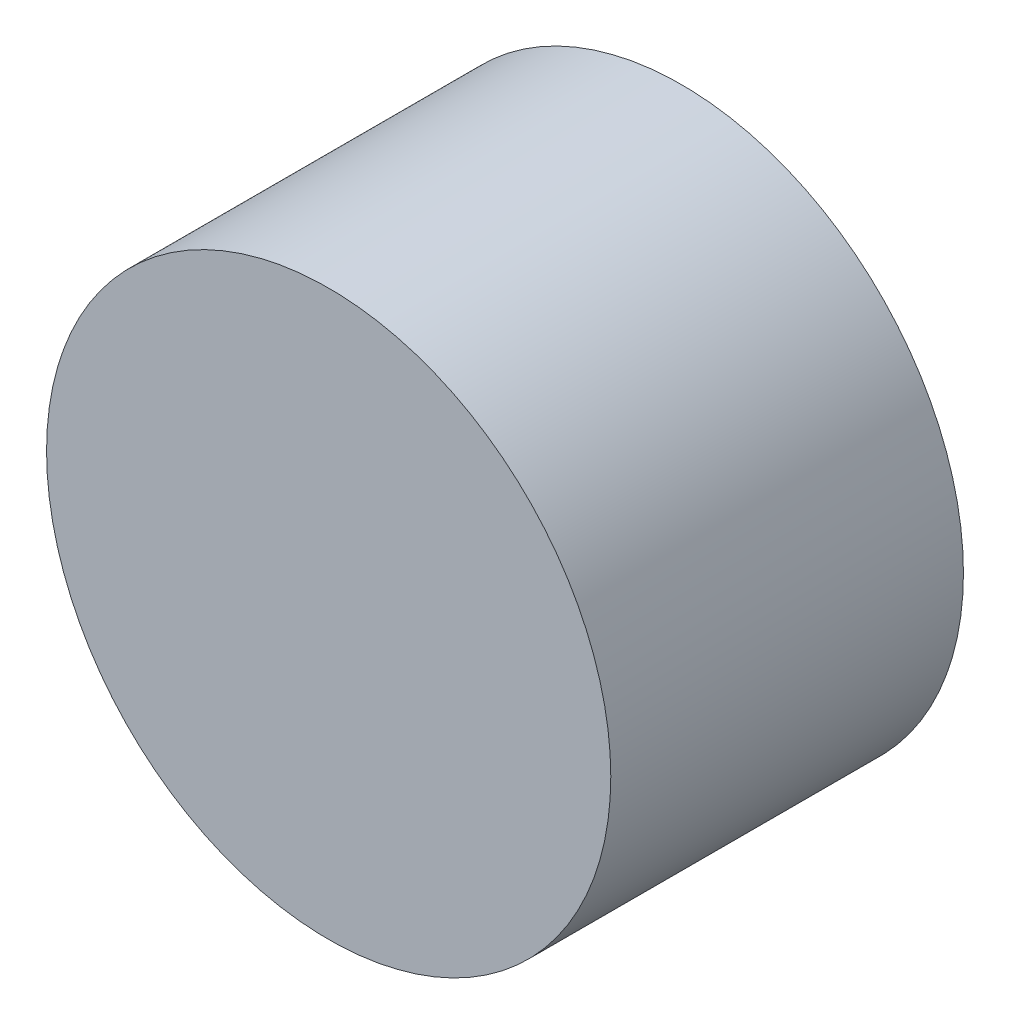
SolidWorks part; units mm, degrees
material "Pure Lead"
ref_plane "XY" through (0, 0, 0) normal (0, 0, 1) x (1, 0, 0)
ref_plane "XZ" through (0, 0, 0) normal (0, 1, 0) x (1, 0, 0)
ref_plane "YZ" through (0, 0, 0) normal (1, 0, 0) x (0, 0, -1)
ref_axis "X" through (-27.94, 0, 0) along (1, 0, 0)
ref_axis "Y" through (0, -27.94, 0) along (0, 1, 0)
ref_axis "Z" through (0, 0, 30.6705) along (0, 0, -1)
sketch "Sketch1" plane through (0, 0, 0) normal (0, 0, 1) x (1, 0, 0)
  circle A0 centre (0, 0) radius 25.4
  dimension "D1" = 50.8
extrude "Boss-Extrude1" add sketch "Sketch1" along normal blind 31.75
